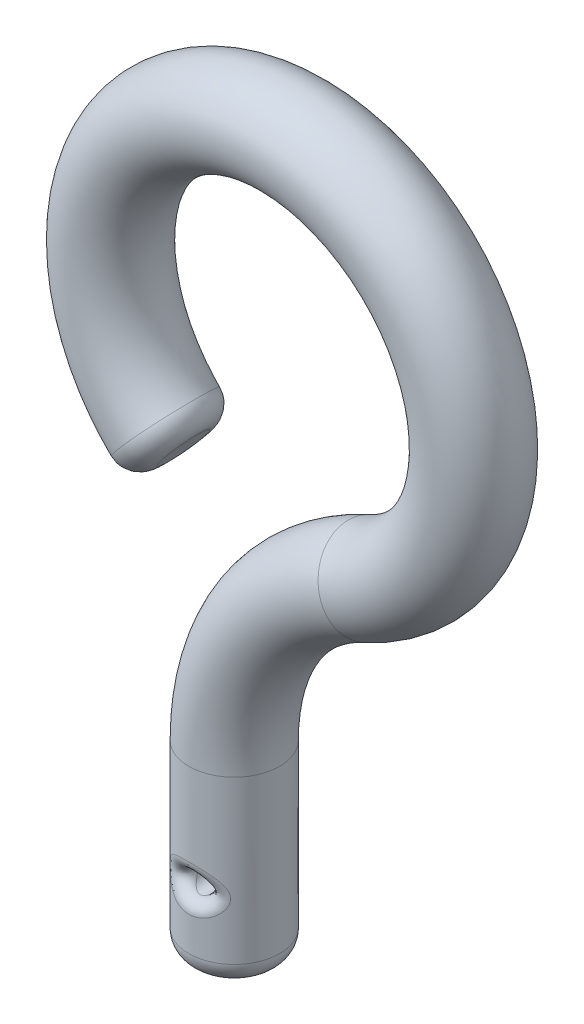
SolidWorks part; units mm, degrees
ref_plane "Спереди" through (0, 0, 0) normal (0, 0, 1) x (1, 0, 0)
ref_plane "Сверху" through (0, 0, 0) normal (0, 1, 0) x (1, 0, 0)
ref_plane "Справа" through (0, 0, 0) normal (1, 0, 0) x (0, 0, -1)
sketch "Эскиз1" plane through (0, 0, 0) normal (0, 1, 0) x (1, 0, 0)
  circle A0 centre (0, 0) radius 2
  dimension "D1" = 4
sketch "Эскиз2" plane through (0, 0, 0) normal (0, 0, 1) x (1, 0, 0)
  line L0 (0, 0) -> (0, 8.149)
  arc A0 (0, 8.149) -> (5.8593, 17.2514) centre (10, 8.149) cw
  arc A1 (5.8593, 17.2514) -> (-2.273, 18.1482) centre (2.5467, 24.5334) ccw
  dimension "D1" = 10
  dimension "D2" = 8
sweep "По траектории1" add profiles "Эскиз1" path "Эскиз2"
sketch "Эскиз3" plane through (0, 0, 0) normal (0, 0, 1) x (1, 0, 0)
  circle A0 centre (0, 3.5) radius 0.5
  dimension "D1" = 1
  dimension "D2" = 3.5
extrude "Вытянуть1" cut sketch "Эскиз3" against normal blind 10 and the other way blind 10
fillet "Скругление1" radius 0.5 2 edges at (0.4903, 3.5979, 1.939) (-0.0978, 3.0097, -1.9976)
fillet "Скругление2" radius 1 2 edges at (0, 0, 2) (-2.273, 18.1482, 2)
